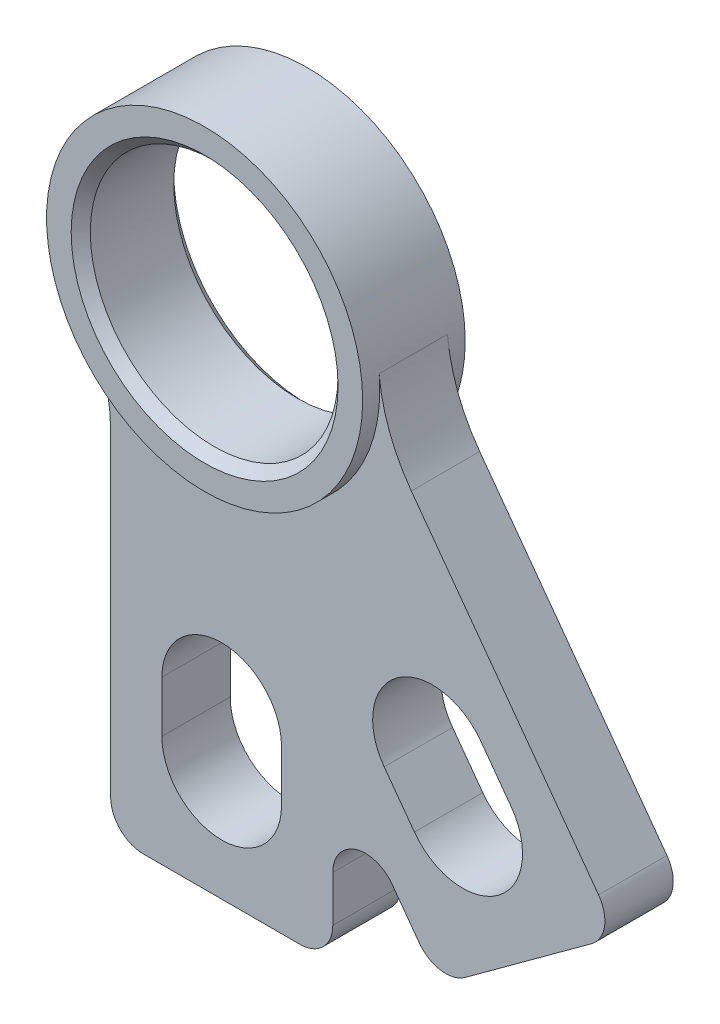
SolidWorks part; units mm, degrees
material "AISI 4130 Steel, annealed at 865C"
ref_plane "X-Y Datum" through (0, 0, 0) normal (0, 0, 1) x (1, 0, 0)
ref_plane "X-Z Datum" through (0, 0, 0) normal (0, 1, 0) x (1, 0, 0)
ref_plane "Y-Z Datum" through (0, 0, 0) normal (1, 0, 0) x (0, 0, -1)
sketch "Sketch1" plane through (0, 0, 0) normal (0, 0, 1) x (1, 0, 0)
  line L0 (0, -37.9413) -> (0, -33.1787) construction
  line L1 (-5.5562, -37.9413) -> (-5.5562, -33.1787)
  line L2 (5.5562, -37.9413) -> (5.5562, -33.1787)
  line L3 (22.3879, -30.632) -> (19.5777, -26.787) construction
  line L4 (17.902, -33.9106) -> (15.0918, -30.0656)
  line L5 (26.8737, -27.3535) -> (24.0635, -23.5085)
  line L6 (-10.3187, -15.7343) -> (-10.3187, -48.26)
  line L7 (-10.3187, -48.26) -> (10.3187, -48.26)
  line L10 (20.1457, -45.0517) -> (36.8075, -32.8742)
  line L11 (36.8075, -32.8742) -> (17.6152, -6.6144)
  line L13 (10.3187, -48.26) -> (10.3187, -31.606)
  line L14 (0, -43.4975) -> (0, -48.26) construction
  line L15 (25.6664, -35.1179) -> (28.4766, -38.9629) construction
  line L16 (25.4686, -25.431) -> (29.3137, -22.6208) construction
  line L17 (-5.5562, -35.56) -> (-10.3187, -35.56) construction
  line L18 (-10.3187, -22.86) -> (10.3187, -22.86) construction
  line L19 (10.3187, -22.86) -> (10.3187, -48.26) construction
  line L20 (5.5562, -35.56) -> (10.3187, -35.56) construction
  line L21 (0, -27.6225) -> (0, -22.86) construction
  line L22 (20.1457, -45.0517) -> (5.158, -24.5449) construction
  line L23 (5.158, -24.5449) -> (21.8198, -12.3674) construction
  line L24 (16.4969, -31.9881) -> (12.6519, -34.7983) construction
  line L25 (16.2991, -22.3012) -> (13.4889, -18.4561) construction
  line L29 (20.1457, -45.0517) -> (10.3187, -31.606)
  line L31 (219.5217, -300.3591) -> (0, 0) construction
  line L32 (0, -364.1414) -> (0, 0) construction
  circle A0 centre (0, 0) radius 11.5062
  arc A1 (-5.5562, -37.9413) -> (5.5562, -37.9413) centre (0, -37.9413) ccw
  arc A2 (5.5562, -33.1787) -> (-5.5562, -33.1787) centre (0, -33.1787) ccw
  arc A3 (17.902, -33.9106) -> (26.8737, -27.3535) centre (22.3879, -30.632) ccw
  arc A4 (24.0635, -23.5085) -> (15.0918, -30.0656) centre (19.5777, -26.787) ccw
  arc A5 (14.6215, 1.3227) -> (-12.5852, -7.5598) centre (0, 0) ccw
  arc A6 (17.6152, -6.6144) -> (14.6215, 1.3227) centre (30.4319, 2.7529) cw
  arc A7 (-10.3187, -15.7343) -> (-12.5852, -7.5598) centre (-26.1937, -15.7343) ccw
  arc A14 (-12.5852, -7.5598) -> (14.6215, 1.3227) centre (0, 0) ccw
  point P5 (0, -35.56)
  point P11 (20.9828, -28.7095)
  point P24 (28.4766, -38.9629)
  point P31 (0, -48.26)
  point P39 (25.6664, -35.1179)
  dimension "D1" = 23.0124
  dimension "D2" = 3.175
  dimension "D8" = 15.875
  dimension "D6" = 22.86
  dimension "D3" = 20.6375
  dimension "D4" = 4.7625
  dimension "D5" = 25.4
  dimension "D7" = 22.86
extrude "Boss-Extrude2" add sketch "Sketch1" along normal mid plane 9.525 contours A5 A14 A0 region at (-4.4276, 13.5615, 0)
extrude "Boss-Extrude3" add sketch "Sketch1<4>" along normal mid plane 6.35 contours A14 A7 L6 L7 L10 L11 A6 A4 L5 A3 L4 A2 L2 A1 L1 region at (8.9526, -27.4215, 0)
sketch "Sketch1<4>" plane through (0, 0, 0) normal (0, 0, 1) x (1, 0, 0) same geometry as "Sketch1"
fillet "Fillet1" radius 3.048 5 edges at (-10.3187, -48.26, 0) (36.8075, -32.8742, 0) (10.3187, -31.606, 0) (10.3187, -48.26, 0) (20.1457, -45.0517, 0)
chamfer "Chamfer1" distance 0.889 angle 45 2 edges at (11.5062, 0, -4.7625) (11.5062, 0, 4.7625)
